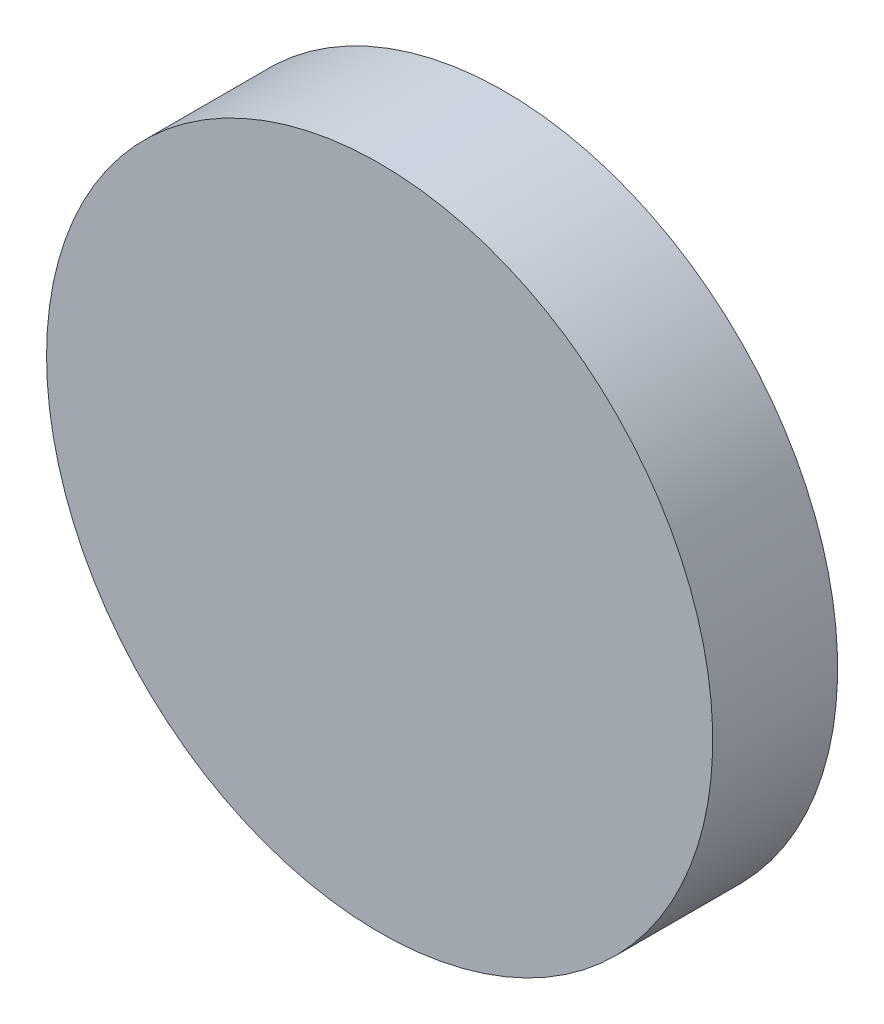
SolidWorks part; units mm, degrees
material "Natural Rubber"
ref_plane "Front Plane" through (0, 0, 0) normal (0, 0, 1) x (1, 0, 0)
ref_plane "Top Plane" through (0, 0, 0) normal (0, 1, 0) x (1, 0, 0)
ref_plane "Right Plane" through (0, 0, 0) normal (1, 0, 0) x (0, 0, -1)
sketch "Sketch1" plane through (0, 0, 0) normal (0, 0, 1) x (1, 0, 0)
  circle A0 centre (0, 0) radius 50.8
  dimension "D1" = 101.6
extrude "Boss-Extrude1" add sketch "Sketch1" along normal blind 19.05
hole_wizard "Ø3.0mm Clearance Dowel Hole1" positions "Sketch2" profile "Sketch3" hole size "Ø3.0" standard "ANSI Metric" end condition through all
sketch "Sketch2" plane through (0, 0, 19.05) normal (0, 0, 1) x (1, 0, 0)
  point P0 (0, 0)
sketch "Sketch3" plane through (0, 0, 19.05) normal (1, 0, 0) x (0, -1, 0)
  line L0 (0, 0) -> (0, 19.05)
  line L1 (0, 19.05) -> (1.5, 19.05)
  line L2 (1.5, 19.05) -> (1.5, 0)
  line L5 (1.5, 0) -> (0, 0)
  line L11 (0, -6.35) -> (0, 107.95) construction
  dimension "Thru Hole Dia." = 3
  dimension "Thru Hole Depth" = 19.05
shell "Shell3" thickness 5 removed face at (1.5, 0, 19.05)
extrude "Boss-Extrude2" add sketch "Sketch1<2>" against normal blind 5 from surface starting at face at (45.8, 0, 19.05)
sketch "Sketch1<2>" plane through (0, 0, 0) normal (0, 0, 1) x (1, 0, 0) same geometry as "Sketch1"
